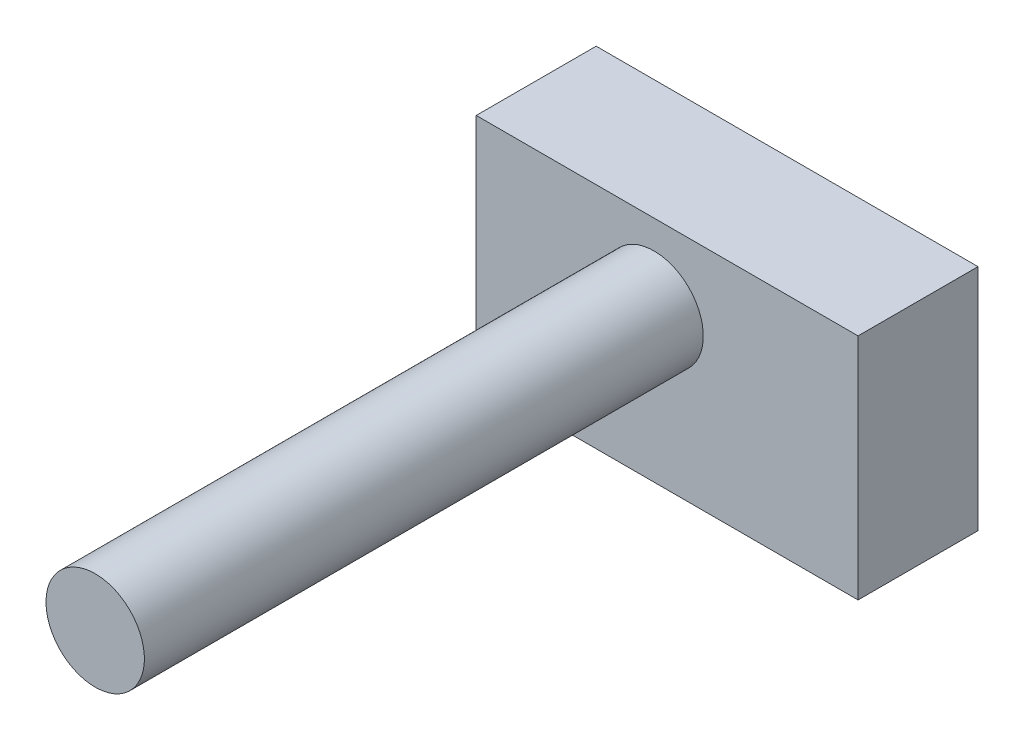
SolidWorks part; units mm, degrees
material "Al-Aly 7075-T7351 Plate per AMS 4078"
ref_plane "Z Plane" through (0, 0, 0) normal (0, 0, 1) x (1, 0, 0)
ref_plane "Y Plane" through (0, 0, 0) normal (0, 1, 0) x (1, 0, 0)
ref_plane "X Plane" through (0, 0, 0) normal (1, 0, 0) x (0, 0, -1)
ref_axis "X Axis" through (-88.99, 0, 0) along (1, 0, 0)
ref_axis "Z Axis" through (0, 0, -88.99) along (0, 0, 1)
ref_axis "Y Axis" through (0, 55, 0) along (0, -1, 0)
sketch "Sketch1" plane through (0, 0, 0) normal (0, 0, 1) x (1, 0, 0)
  line L1 (-80.8622, -48.4364) -> (80.8622, -48.4364)
  line L2 (-80.8622, -48.4364) -> (-80.8622, 48.4364)
  line L3 (-80.8622, 48.4364) -> (80.8622, 48.4364)
  line L4 (80.8622, -48.4364) -> (80.8622, 48.4364)
  line L5 (-80.8622, -48.4364) -> (80.8622, 48.4364) construction
  line L6 (-80.8622, 48.4364) -> (80.8622, -48.4364) construction
  point P0 (0, 0)
extrude "Boss-Extrude1" add sketch "Sketch1" along normal blind 50.8
sketch "Sketch2" plane through (0, 0, 50.8) normal (0, 0, 1) x (1, 0, 0)
  circle A0 centre (-5.5257, 15.5605) radius 20.831
extrude "Boss-Extrude2" add sketch "Sketch2" along normal blind 236.728 contours A0
